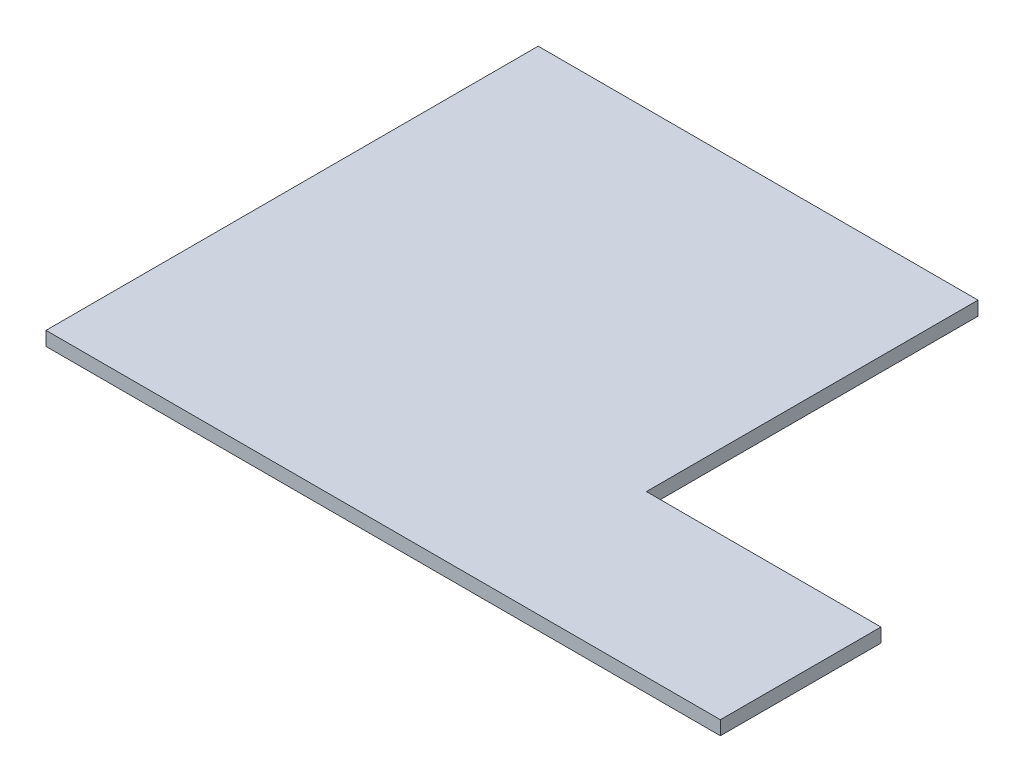
SolidWorks part; units mm, degrees
material "橡木"
ref_plane "前视基准面" through (0, 0, 0) normal (0, 0, 1) x (1, 0, 0)
ref_plane "上视基准面" through (0, 0, 0) normal (0, 1, 0) x (1, 0, 0)
ref_plane "右视基准面" through (0, 0, 0) normal (1, 0, 0) x (0, 0, -1)
other "Configuration Table"
sketch "草图1" plane through (0, 0, 0) normal (0, 1, 0) x (1, 0, 0)
  line L1 (0, 0) -> (630, 0)
  line L2 (0, 0) -> (0, 705)
  line L3 (0, 705) -> (630, 705)
  line L4 (630, 230) -> (630, 705)
  line L5 (630, 0) -> (966, 0)
  line L7 (630, 230) -> (966, 230)
  line L8 (966, 0) -> (966, 230)
  dimension "D1" = 630
  dimension "D2" = 705
  dimension "D3" = 336
  dimension "D4" = 230
extrude "凸台-拉伸1" add sketch "草图1" along normal blind 20
